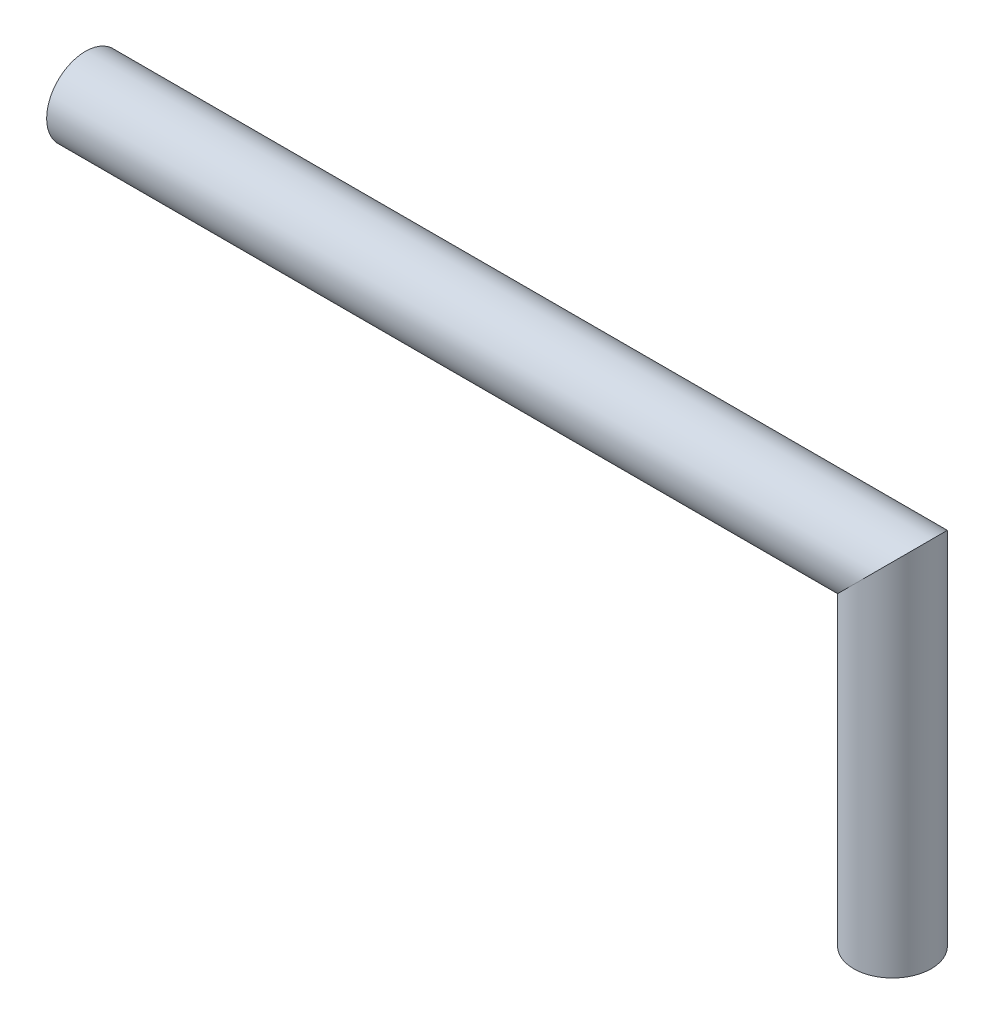
SolidWorks part; units mm, degrees
ref_plane "Front Plane" through (0, 0, 0) normal (0, 0, 1) x (1, 0, 0)
ref_plane "Top Plane" through (0, 0, 0) normal (0, 1, 0) x (1, 0, 0)
ref_plane "Right Plane" through (0, 0, 0) normal (1, 0, 0) x (0, 0, -1)
sketch "Sketch1" plane through (0, 0, 0) normal (0, 0, 1) x (1, 0, 0)
  line L0 (-73.9275, 0) -> (0, 0)
  line L1 (0, 0) -> (0, -30.4929)
sweep "Sweep2" add path "Sketch1" circular profile diameter 7.112 parameters "D3"=7.112
